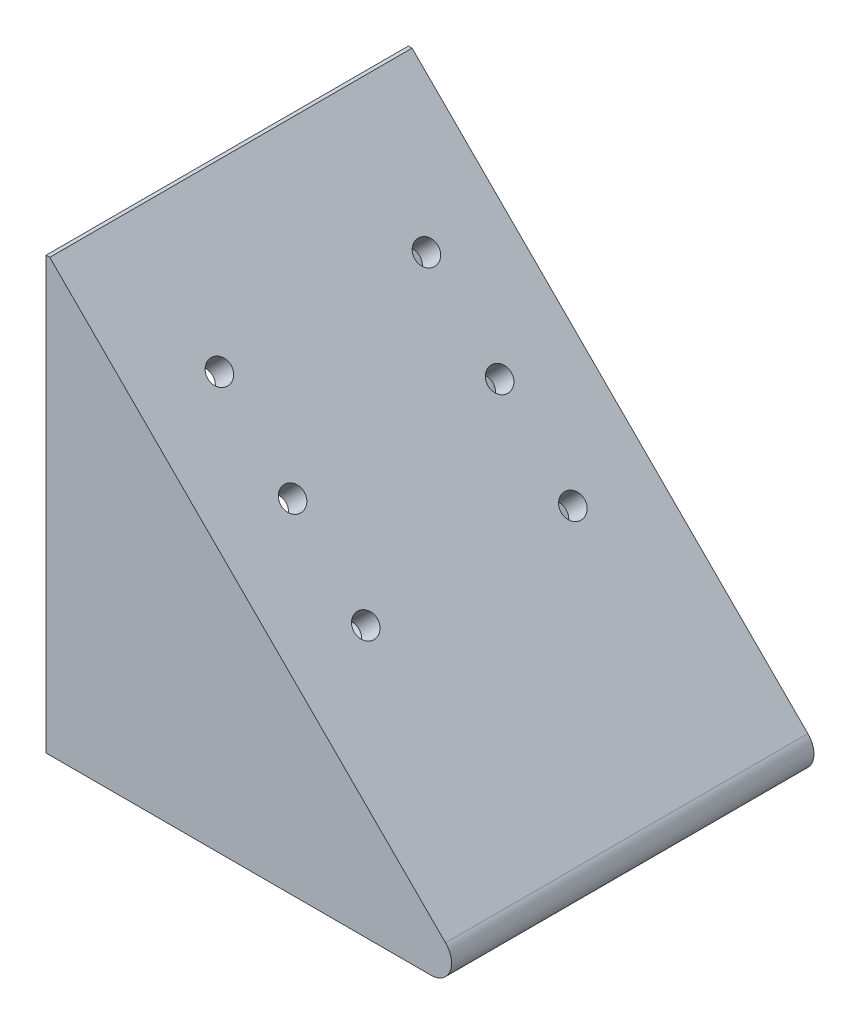
SolidWorks part; units mm, degrees
ref_plane "前视基准面" through (0, 0, 0) normal (0, 0, 1) x (1, 0, 0)
ref_plane "上视基准面" through (0, 0, 0) normal (0, 1, 0) x (1, 0, 0)
ref_plane "右视基准面" through (0, 0, 0) normal (1, 0, 0) x (0, 0, -1)
sketch "草图1" plane through (0, 0, 0) normal (0, 0, 1) x (1, 0, 0)
  line L0 (0, 0) -> (84, 0)
  line L1 (84, 0) -> (0, 84)
  line L2 (0, 84) -> (0, 0)
  dimension "D1" = 84
  dimension "D2" = 84
extrude "凸台-拉伸1" add sketch "草图1" along normal blind 70
fillet "圆角1" radius 4 1 edges at (84, 0, 35)
chamfer "倒角1" distance 1 angle 45 1 edges at (0, 84, 35) first distance on face at (38.5858, 45.4142, 35)
shell "抽壳1" thickness 5 removed face at (0, 41.6464, 35)
hole_wizard "Ø4.5 (4.5) 直径孔1" positions "草图3" profile "草图2" hole size "Ø4.5" standard "GB"
sketch "草图3" plane through (42, 42, 0) normal (0.7071, 0.7071, 0) x (0.7071, -0.7071, 0)
  line L0 (-58.397, -35) -> (49.7401, -35) construction
  line L1 (-58.397, 0) -> (-58.397, -70) construction
  line L2 (49.7401, -70) -> (49.7401, 0) construction
  line L3 (49.7401, -70) -> (-58.397, -70) construction
  point P0 (-33.2599, -55)
  point P2 (-13.2599, -55)
  point P4 (6.7401, -55)
  point P22 (6.7401, -15)
  point P23 (-13.2599, -15)
  point P24 (-33.2599, -15)
  dimension "D1" = 20
  dimension "D2" = 20
  dimension "D3" = 15
  dimension "D4" = 43
sketch "草图2" plane through (18.4817, 65.5183, 55) normal (0, 0, 1) x (-0.7071, 0.7071, 0)
  line L0 (0, 0) -> (0, 11.3519)
  line L1 (0, 11.3519) -> (2.25, 10)
  line L2 (2.25, 10) -> (2.25, 0)
  line L5 (2.25, 0) -> (0, 0)
  line L10 (0, 11.3519) -> (-2.25, 10) construction
  line L11 (0, -6.35) -> (0, 107.95) construction
  dimension "孔直径" = 4.5
  dimension "孔深度" = 10
  dimension "导头角度" = 118
